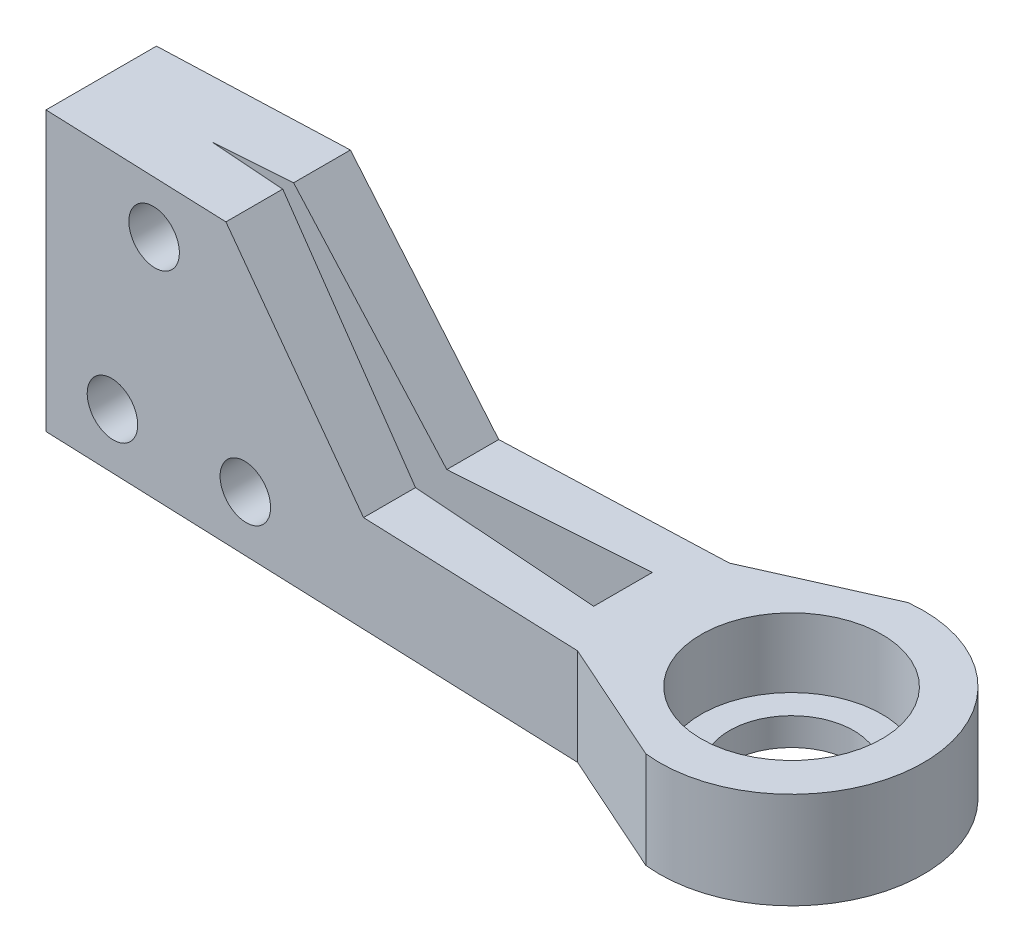
SolidWorks part; units mm, degrees
ref_plane "Front Plane" through (0, 0, 0) normal (0, 0, 1) x (1, 0, 0)
ref_plane "Top Plane" through (0, 0, 0) normal (0, 1, 0) x (1, 0, 0)
ref_plane "Right Plane" through (0, 0, 0) normal (1, 0, 0) x (0, 0, -1)
sketch "Sketch8" plane through (0, 0, 0) normal (0, 1, 0) x (1, 0, 0)
  line L0 (0, -4) -> (0, 4)
  line L1 (0, 4) -> (48.9352, 9.4905)
  line L2 (0, 0) -> (54.3416, 0) construction
  line L3 (0, -4) -> (48.9352, -9.4905)
  line L4 (0, 0) -> (40, 0) construction
  line L5 (0, 4) -> (40, 5.5)
  line L6 (40, 5.5) -> (48.9352, 9.4905)
  line L7 (0, -4) -> (40, -5.5)
  line L8 (40, -5.5) -> (48.9352, -9.4905)
  circle A0 centre (50, 0) radius 4.5
  arc A1 (48.9352, -9.4905) -> (48.9352, 9.4905) centre (50, 0) ccw
  circle A2 centre (50, 0) radius 6.55 construction
  point P3 (0, 0)
  dimension "D1" = 9
  dimension "D4" = 3
  dimension "D6" = 13.1
  dimension "D2" = 40
  dimension "D3" = 10
  dimension "D5" = 8
  dimension "D7" = 11
extrude "Boss-Extrude2" add sketch "Sketch8" along normal blind 7 contours L8 A1 L6 L5 L0 L7 A0 region at (31.8889, 0, 0)
sketch "Sketch10" plane through (0, 7, 0) normal (0, 1, 0) x (1, 0, 0)
  circle A0 centre (50, 0) radius 6.55
  dimension "D1" = 13.1
extrude "Cut-Extrude6" cut sketch "Sketch10" against normal blind 5
sketch "Sketch11" plane through (0, 0, 0) normal (0, 0, 1) x (1, 0, 0)
  line L0 (0, 4) -> (33.2898, 4) construction
  circle A0 centre (5, 4) radius 1.9
  circle A1 centre (15, 4) radius 1.9
  dimension "D1" = 3.8
  dimension "D2" = 10
  dimension "D3" = 5
  dimension "D4" = 4
extrude "Cut-Extrude7" cut sketch "Sketch11" against normal blind 10 and the other way blind 10
sketch "Sketch12" plane through (0, 0, 0) normal (0, 0, 1) x (1, 0, 0)
  line L0 (23.8949, 7) -> (13.5404, 20.178)
  line L1 (0, 7) -> (40, 7) construction
  line L2 (13.5404, 20.178) -> (0, 20.178)
  line L3 (0, 20.178) -> (0, 7)
  line L4 (6.7702, 20.178) -> (11.5589, 7) construction
  line L5 (0, 7) -> (23.8949, 7)
  circle A0 centre (8.1364, 16.4185) radius 1.9
  point P11 (8.5104, 15.9748)
  point P12 (7.4127, 19.9985)
  point P13 (12.0772, 21.8557)
  point P14 (7.7248, 17.3182)
  point P15 (6.7702, 20.178)
  dimension "D1" = 3.8
  dimension "D2" = 4
extrude "Boss-Extrude3" add sketch "Sketch12" along normal up to surface and the other way up to surface up to face at (3.1, 4, 4.1162) other way up to face at (6.9, 4, -4.2588)
sketch "Sketch13" plane through (0, 0, 0) normal (0, 1, 0) x (1, 0, 0)
  line L0 (8.0188, 0) -> (37.7929, 2.1267)
  line L1 (37.7929, 2.1267) -> (37.7929, -2.1267)
  line L2 (37.7929, -2.1267) -> (8.0188, 0)
  line L3 (0, 0) -> (65.8394, 0) construction
  point P6 (16.5766, 0)
  point P7 (37.7929, 0)
  point P8 (38.1324, -2.9688)
  point P9 (15.246, 0)
  point P10 (10.1748, 0)
  point P11 (8.0188, 0)
  point P12 (39.3791, 2.352)
  point P13 (37.4191, 2.842)
  point P14 (38.2031, 2.156)
extrude "Cut-Extrude8" cut sketch "Sketch13" along normal up to surface (20.178 mm away) up to face at (6.7702, 20.178, 0)
